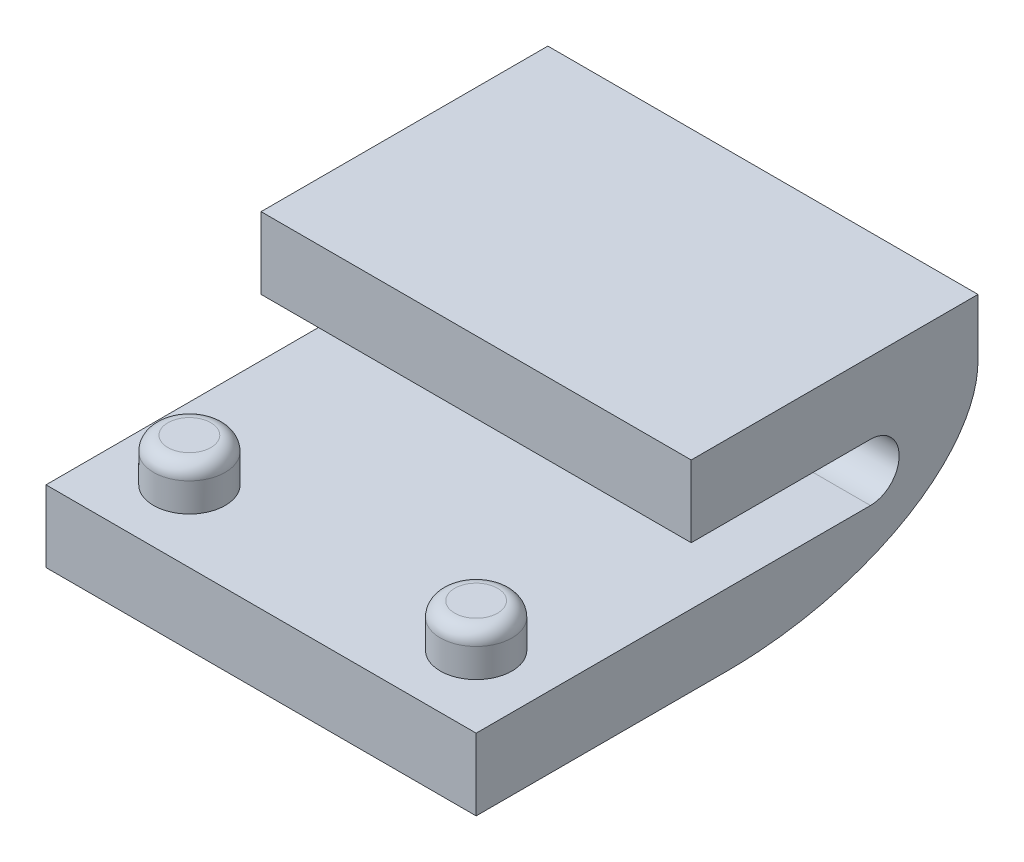
SolidWorks part; units mm, degrees
ref_plane "Plano frontal" through (0, 0, 0) normal (0, 0, 1) x (1, 0, 0)
ref_plane "Plano superior" through (0, 0, 0) normal (0, 1, 0) x (1, 0, 0)
ref_plane "Plano direito" through (0, 0, 0) normal (1, 0, 0) x (0, 0, -1)
sketch "Esboço1" plane through (0, 0, 0) normal (1, 0, 0) x (0, 0, -1)
  line L0 (0, 0) -> (4, 0)
  line L1 (4, 0) -> (4, -2.8)
  line L2 (4, -2.8) -> (-3, -2.8)
  line L3 (-3, -2.8) -> (-3, -1.8)
  line L4 (-3, -1.8) -> (2.5, -1.8)
  line L5 (2.5, -1.8) -> (2.5, -1)
  line L6 (2.5, -1) -> (0, -1)
  line L7 (0, -1) -> (0, 0)
  point P7 (0, 0)
  dimension "D1" = 1
  dimension "D2" = 7
  dimension "D3" = 1
  dimension "D4" = 4
  dimension "D5" = 0.8
  dimension "D6" = 1.5
extrude "Ressalto-extrusão1" add sketch "Esboço1" along normal mid plane 6
fillet "Filete1" radius 3.5 1 edges at (0, -2.8, -4) second distance 2 first distance on face at (0, -2.8, -0.5)
sketch "Esboço2" plane through (0, -1.8, 0) normal (0, 1, 0) x (1, 0, 0)
  line L0 (-3, 2.5) -> (-3, -3) construction
  line L1 (3, -3) -> (-3, -3) construction
  circle A0 centre (-2, -2) radius 0.5
  dimension "D1" = 1
  dimension "D3" = 1
  dimension "D2" = 1
extrude "Ressalto-extrusão4" add sketch "Esboço2" along normal blind 0.6 contours A0
sketch "Esboço3" plane through (0, -1, 0) normal (0, -1, 0) x (1, 0, 0)
  line L0 (3, 0) -> (-3, 0) construction
  line L1 (-3, 0) -> (-3, -2.5) construction
  circle A0 centre (-2, -1) radius 0.5
  dimension "D1" = 1
  dimension "D2" = 1
  dimension "D3" = 1
extrude "Ressalto-extrusão5" add sketch "Esboço3" along normal blind 0.4
fillet "Filete2" radius 0.2 2 edges at (-2, -1.2, 2.5) (-2, -1.4, -1.5)
mirror "Espelhar1" about plane through (0, 0, 0) normal (1, 0, 0) of "Ressalto-extrusão5", "Filete2", "Ressalto-extrusão4"
sketch "Esboço4" plane through (-3, 0, 0) normal (-1, 0, 0) x (0, 0, 1)
  line L0 (-2.5, -1) -> (-2.5, -1.8) construction
  circle A0 centre (-2.5, -1.4) radius 0.4
  dimension "D1" = 0.8
extrude "Corte-extrusão1" cut sketch "Esboço4" against normal through all
